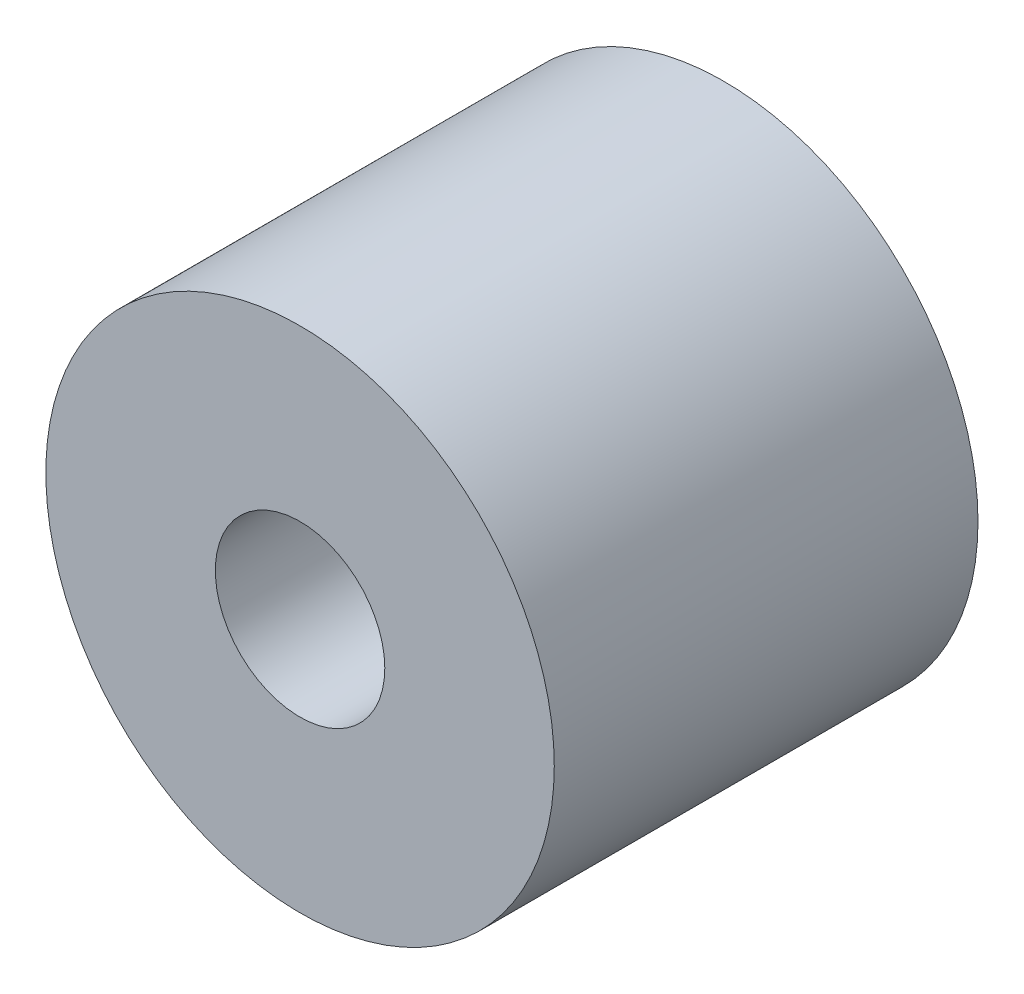
SolidWorks part; units mm, degrees
material "Manganese Bronze"
ref_plane "Front Plane" through (0, 0, 0) normal (0, 0, 1) x (1, 0, 0)
ref_plane "Top Plane" through (0, 0, 0) normal (0, 1, 0) x (1, 0, 0)
ref_plane "Right Plane" through (0, 0, 0) normal (1, 0, 0) x (0, 0, -1)
sketch "Sketch1" plane through (0, 0, 0) normal (0, 0, 1) x (1, 0, 0)
  circle A0 centre (0, 0) radius 12
  circle A1 centre (0, 0) radius 4
extrude "Boss-Extrude1" add sketch "Sketch1" along normal blind 20
